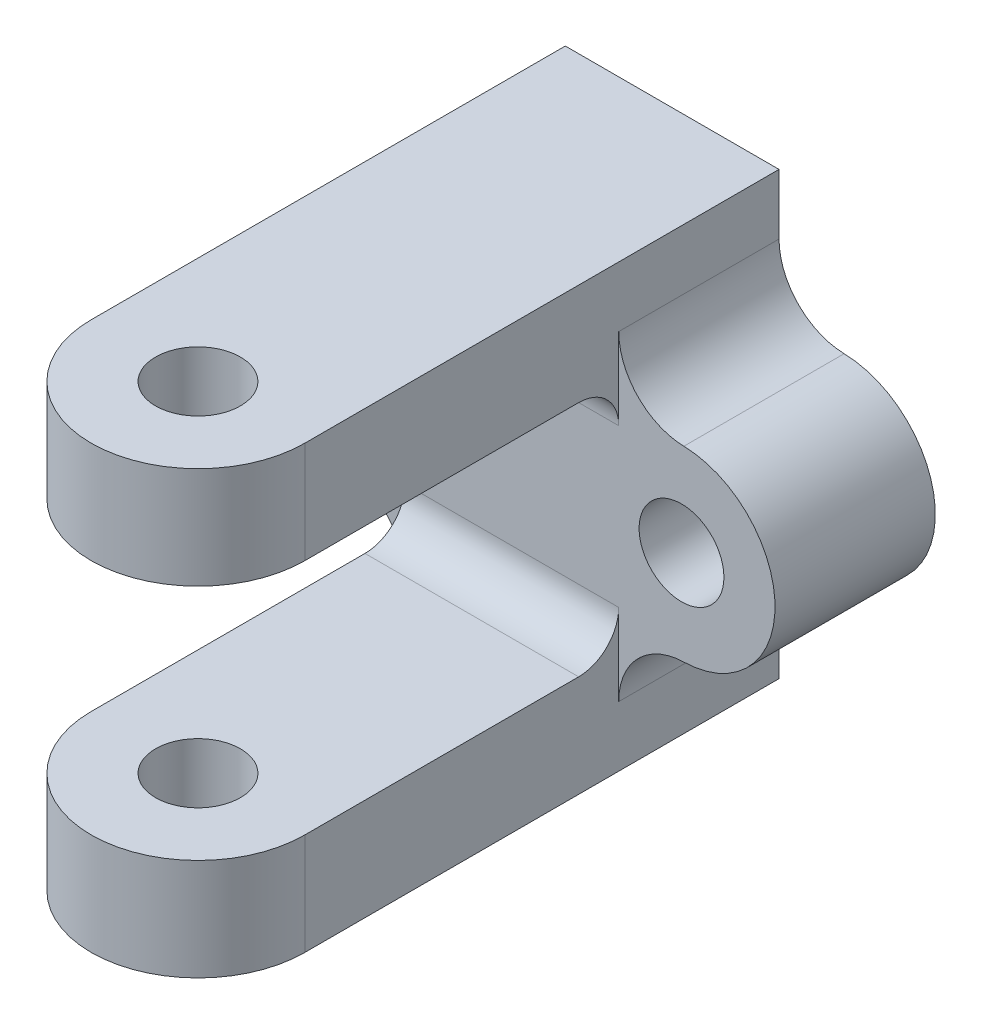
SolidWorks part; units mm, degrees
material "7075-T6 (SN)"
ref_plane "Front Plane" through (0, 0, 0) normal (0, 0, 1) x (1, 0, 0)
ref_plane "Top Plane" through (0, 0, 0) normal (0, 1, 0) x (1, 0, 0)
ref_plane "Right Plane" through (0, 0, 0) normal (1, 0, 0) x (0, 0, -1)
sketch "Sketch1" plane through (0, 0, 0) normal (0, 0, 1) x (1, 0, 0)
  line L0 (12.7, 0) -> (-12.7, 0) construction
  line L1 (-20.7, -16.51) -> (20.7, -16.51)
  line L2 (-20.7, -16.51) -> (-20.7, 16.51)
  line L3 (-20.7, 16.51) -> (20.7, 16.51)
  line L4 (20.7, -16.51) -> (20.7, 16.51)
  line L5 (-20.7, -16.51) -> (20.7, 16.51) construction
  line L6 (-20.7, 16.51) -> (20.7, -16.51) construction
  circle A0 centre (12.7, 0) radius 3.175
  circle A1 centre (-12.7, 0) radius 3.175
  point P0 (0, 0)
  dimension "D1" = 6.35
  dimension "D2" = 25.4
  dimension "D3" = 8
  dimension "D4" = 16.51
extrude "Boss-Extrude1" add sketch "Sketch1" along normal blind 12
sketch "Sketch2" plane through (0, 0, 12) normal (0, 0, 1) x (1, 0, 0)
  line L0 (-12.7, 0) -> (12.7, 0) construction
  line L2 (-20.7, 8.89) -> (20.7, 8.89)
  line L3 (-20.7, 8.89) -> (-20.7, 16.51)
  line L4 (-20.7, 16.51) -> (20.7, 16.51)
  line L5 (20.7, 8.89) -> (20.7, 16.51)
  line L6 (-20.7, 8.89) -> (20.7, 16.51) construction
  line L7 (-20.7, 16.51) -> (20.7, 8.89) construction
  line L8 (-20.7, 16.51) -> (-20.7, -16.51) construction
  line L9 (20.7, -8.89) -> (20.7, -16.51)
  line L10 (-20.7, -8.89) -> (-20.7, -16.51)
  line L11 (-20.7, -16.51) -> (20.7, -8.89) construction
  line L12 (-20.7, -8.89) -> (20.7, -16.51) construction
  line L13 (-20.7, -8.89) -> (20.7, -8.89)
  line L14 (-20.7, -16.51) -> (20.7, -16.51)
  circle A0 centre (-12.7, 0) radius 3.175 construction
  circle A1 centre (12.7, 0) radius 3.175 construction
  point P6 (0, 12.7)
  point P21 (0, -12.7)
  dimension "D1" = 17.78
extrude "Boss-Extrude2" add sketch "Sketch2" along normal blind 53
sketch "Sketch3" plane through (0, 0, 0) normal (0, 1, 0) x (1, 0, 0)
  point P0 (0, -35.5)
  dimension "D1" = 35.5
ref_point "UBJ Point"
sketch "Sketch4" plane through (0, 0, 0) normal (0, 1, 0) x (1, 0, 0)
  circle A0 centre (0, -35.5) radius 3.175
  dimension "D1" = 6.35
extrude "Cut-Extrude1" cut sketch "Sketch4" against normal up to surface and the other way up to surface up to face at (0, -16.51, 32.5) other way up to face at (0, 16.51, 32.5)
sketch "Sketch5" plane through (0, 0, 0) normal (0, 1, 0) x (1, 0, 0)
  line L0 (20.7, -12) -> (8.3595, -39.2814)
  line L1 (-8.3595, -39.2814) -> (-20.7, -12)
  line L4 (20.7, 0) -> (-20.7, 0)
  line L5 (-20.7, 0) -> (-20.7, -65)
  line L6 (-20.7, -65) -> (20.7, -65)
  line L7 (20.7, -65) -> (20.7, 0)
  line L9 (-20.7, -12) -> (-20.7, -65)
  line L10 (-20.7, -65) -> (20.7, -65)
  line L11 (20.7, -65) -> (20.7, -12)
  line L12 (20.7, -12) -> (-20.7, -12)
  line L13 (20.7, -65) -> (20.7, -12)
  line L14 (-20.7, -65) -> (20.7, -65)
  line L15 (-20.7, -12) -> (-20.7, -65)
  line L17 (20.7, -65) -> (20.7, -12)
  line L18 (-20.7, -65) -> (20.7, -65)
  line L19 (-20.7, -12) -> (-20.7, -65)
  arc A0 (-8.3595, -39.2814) -> (8.3595, -39.2814) centre (0, -35.5) ccw
  circle A1 centre (0, -35.5) radius 3.175 construction
  circle A2 centre (0, -35.5) radius 3.175 construction
  dimension "D3" = 6
  dimension "D1" = 0
  dimension "D2" = 0
extrude "Cut-Extrude2" [suppressed] cut sketch "Sketch5" against normal up to surface and the other way up to surface contours A0 L1 L9 L10 L11 L0 up to face at (0, -16.51, 38.675) other way up to face at (0, 16.51, 32.325)
sketch "Sketch6" plane through (0, 0, 0) normal (0, 1, 0) x (1, 0, 0)
  line L0 (-8, -35.5) -> (-8, -20)
  line L1 (8, -35.5) -> (8, -20)
  line L2 (-16, -12) -> (-20.7, -12)
  line L3 (-8, -20) -> (-8, -12)
  line L4 (20.7, -12) -> (-20.7, -12)
  line L5 (-20.7, -12) -> (-20.7, -65)
  line L6 (-20.7, -65) -> (20.7, -65)
  line L7 (20.7, -65) -> (20.7, -12)
  line L8 (20.7, -12) -> (16, -12)
  line L9 (-20.7, -12) -> (-20.7, -65)
  line L10 (-20.7, -65) -> (20.7, -65)
  line L11 (20.7, -65) -> (20.7, -12)
  line L12 (-8, -12) -> (-16, -12)
  line L13 (8, -20) -> (8, -12)
  line L14 (8, -12) -> (16, -12)
  arc A0 (-8, -35.5) -> (8, -35.5) centre (0, -35.5) ccw
  circle A1 centre (0, -35.5) radius 3.175 construction
  arc A2 (-8, -20) -> (-16, -12) centre (-16, -20) ccw construction
  arc A3 (8, -20) -> (16, -12) centre (16, -20) cw construction
  dimension "D2" = 8
  dimension "D3" = 8
  dimension "D1" = 0
extrude "Cut-Extrude3" cut sketch "Sketch6" against normal up to surface and the other way up to surface up to face at (0, -16.51, 38.675) other way up to face at (0, 16.51, 32.325)
fillet "Fillet1" [suppressed] radius 12.7
sketch "Sketch7" plane through (0, 0, 0) normal (0, 0, 1) x (1, 0, 0)
  line L0 (-12.7, 7) -> (-8, 7)
  line L1 (-12.7, -7) -> (-8, -7)
  line L2 (-8, 16.51) -> (-8, 7)
  line L3 (-8, -16.51) -> (-8, -7)
  line L4 (0, 10.3988) -> (0, -8.4154) construction
  line L5 (8, -16.51) -> (8, -7)
  line L6 (20.7, -16.51) -> (8, -16.51)
  line L7 (20.7, 16.51) -> (20.7, -16.51)
  line L8 (8, 16.51) -> (20.7, 16.51)
  line L9 (8, 16.51) -> (8, 7)
  line L10 (12.7, 7) -> (8, 7)
  line L11 (12.7, -7) -> (8, -7)
  line L12 (8, 8.89) -> (-8, 8.89)
  line L13 (-8, 8.89) -> (-8, 16.51)
  line L14 (-8, 16.51) -> (-20.7, 16.51)
  line L15 (-20.7, 16.51) -> (-20.7, -16.51)
  line L16 (-20.7, -16.51) -> (-8, -16.51)
  line L17 (-8, -16.51) -> (-8, -8.89)
  line L18 (-8, -8.89) -> (8, -8.89)
  line L19 (8, -8.89) -> (8, -16.51)
  line L20 (8, -16.51) -> (20.7, -16.51)
  line L21 (20.7, -16.51) -> (20.7, 16.51)
  line L22 (20.7, 16.51) -> (8, 16.51)
  line L23 (8, 16.51) -> (8, 8.89)
  line L26 (-8, 16.51) -> (-20.7, 16.51)
  line L27 (-20.7, 16.51) -> (-20.7, -16.51)
  line L28 (-20.7, -16.51) -> (-8, -16.51)
  line L32 (8, -16.51) -> (20.7, -16.51)
  line L33 (20.7, -16.51) -> (20.7, 16.51)
  line L34 (20.7, 16.51) -> (8, 16.51)
  line L36 (-8, 8.89) -> (8, 8.89) construction
  line L37 (8, -8.89) -> (-8, -8.89) construction
  line L38 (-8, 8.89) -> (8, 8.89)
  line L39 (8, -8.89) -> (-8, -8.89)
  arc A0 (-12.7, 7) -> (-12.7, -7) centre (-12.7, 0) ccw
  circle A1 centre (-12.7, 0) radius 3.175 construction
  arc A2 (12.7, 7) -> (12.7, -7) centre (12.7, 0) cw
  dimension "D2" = 7
  dimension "D1" = 0
extrude "Cut-Extrude4" cut sketch "Sketch7" along normal up to surface (12 mm away) contours A0 L0 L2 L26 L27 L28 L3 L1 | L10 A2 L11 L5 L6 L7 L8 L9 region at (-20.0538, 0, 0) region at (8.3538, 12.7, 0) up to face at (0, 0, 12)
fillet "Fillet2" radius 5 4 edges at (8, -7, 6) (8, 7, 6) (-8, 7, 6) (-8, -7, 6)
fillet "Fillet3" radius 3 2 edges at (0, 8.89, 12) (0, -8.89, 12)
